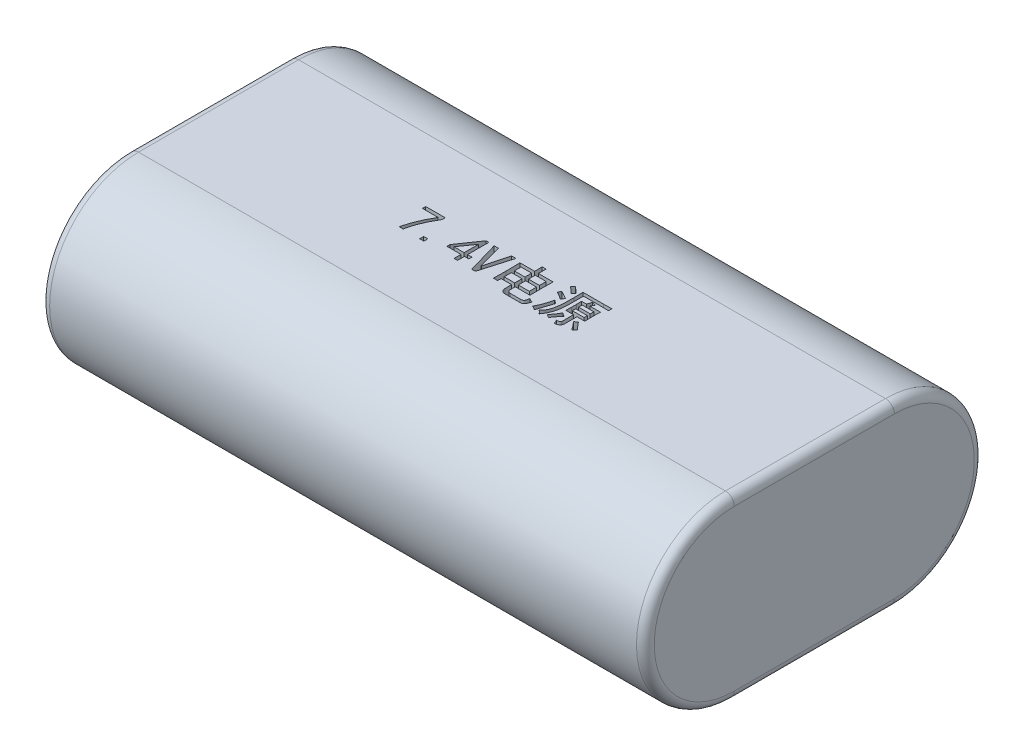
SolidWorks part; units mm, degrees
ref_plane "前视基准面" through (0, 0, 0) normal (0, 0, 1) x (1, 0, 0)
ref_plane "上视基准面" through (0, 0, 0) normal (0, 1, 0) x (1, 0, 0)
ref_plane "右视基准面" through (0, 0, 0) normal (1, 0, 0) x (0, 0, -1)
sketch "草图1" plane through (0, 0, 0) normal (1, 0, 0) x (0, 0, -1)
  line L0 (-13.3184, 6.9379) -> (4.6816, 6.9379) construction
  line L1 (-13.3184, 16.9379) -> (4.6816, 16.9379)
  line L2 (-13.3184, -3.0621) -> (4.6816, -3.0621)
  arc A0 (-13.3184, 16.9379) -> (-13.3184, -3.0621) centre (-13.3184, 6.9379) ccw
  arc A1 (4.6816, -3.0621) -> (4.6816, 16.9379) centre (4.6816, 6.9379) ccw
  point P2 (-4.3184, 6.9379)
  point P7 (14.6816, 6.9379)
  point P8 (-23.3184, 6.9379)
  dimension "D1" = 38
  dimension "D2" = 20
extrude "凸台-拉伸1" add sketch "草图1" along normal blind 68
fillet "圆角1" radius 1 8 edges at (0, -3.0621, 4.3184) (0, 6.9379, -14.6816) (0, 16.9379, 4.3184) (0, 6.9379, 23.3184) (68, 16.9379, 4.3184) (68, 6.9379, -14.6816) (68, -3.0621, 4.3184) (68, 6.9379, 23.3184)
sketch "草图2" plane through (0, 16.9379, 0) normal (0, 1, 0) x (1, 0, 0)
  text T0 "7.4V电源" font "黑体" height 3.5
extrude "切除-拉伸1" cut sketch "草图2" against normal blind 2
